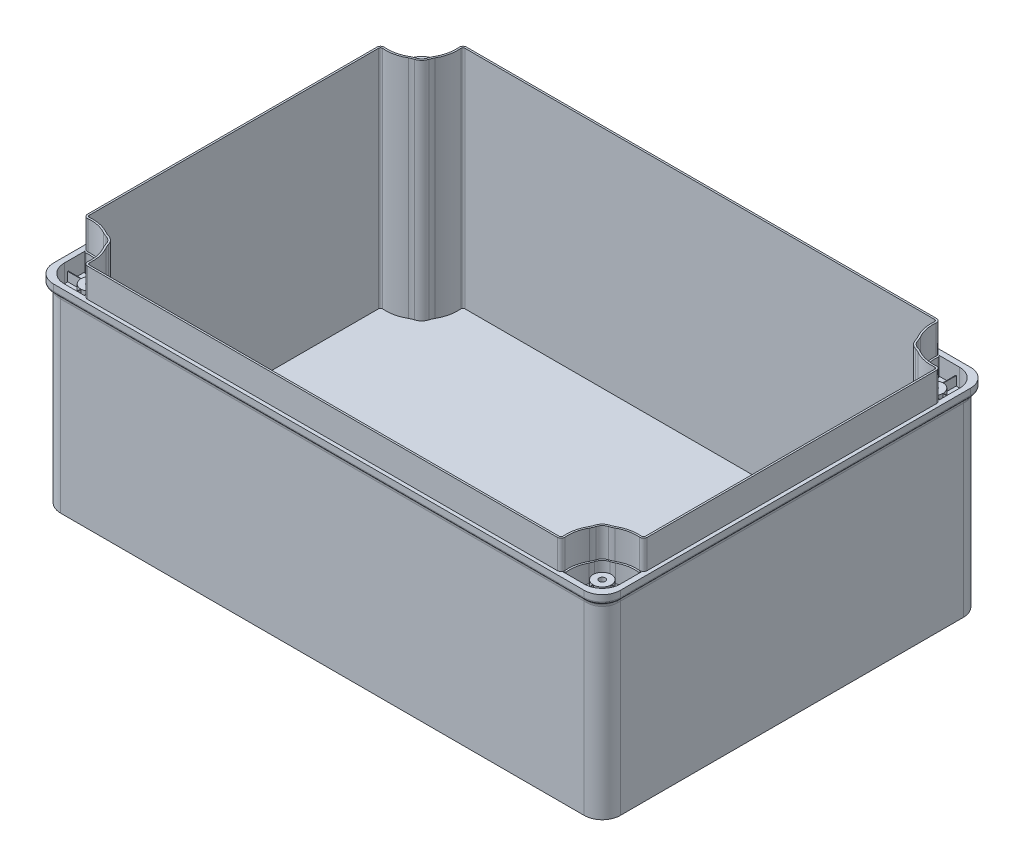
SolidWorks part; units mm, degrees
ref_plane "Alzado" through (0, 0, 0) normal (0, 0, 1) x (1, 0, 0)
ref_plane "Planta" through (0, 0, 0) normal (0, 1, 0) x (1, 0, 0)
ref_plane "Vista lateral" through (0, 0, 0) normal (1, 0, 0) x (0, 0, -1)
sketch "Croquis1" plane through (0, 0, 0) normal (0, 1, 0) x (1, 0, 0)
  line L0 (-154, 94) -> (-154, -94)
  line L1 (-145, 105) -> (145, 105)
  line L2 (-155, 95) -> (-155, -95)
  line L3 (-145, -105) -> (145, -105)
  line L4 (155, 95) -> (155, -95)
  line L5 (-155, 105) -> (155, -105) construction
  line L6 (-155, -105) -> (155, 105) construction
  line L7 (-144, -104) -> (144, -104)
  line L8 (154, 94) -> (154, -94)
  line L9 (-144, 104) -> (144, 104)
  line L10 (-155, 105) -> (-155, -105) construction
  line L11 (-155, -105) -> (155, -105) construction
  line L12 (-154, 104) -> (-154, -104) construction
  line L13 (-154, -104) -> (154, -104) construction
  line L14 (154, 104) -> (154, -104) construction
  line L15 (155, 105) -> (155, -105) construction
  line L16 (-154, 104) -> (154, 104) construction
  line L17 (-155, 105) -> (155, 105) construction
  arc A0 (-155, -95) -> (-145, -105) centre (-145, -95) ccw
  arc A1 (-154, -94) -> (-144, -104) centre (-144, -94) ccw
  arc A2 (144, -104) -> (154, -94) centre (144, -94) ccw
  arc A3 (145, -105) -> (155, -95) centre (145, -95) ccw
  arc A4 (154, 94) -> (144, 104) centre (144, 94) ccw
  arc A5 (145, 105) -> (155, 95) centre (145, 95) cw
  arc A6 (-145, 105) -> (-155, 95) centre (-145, 95) ccw
  arc A7 (-154, 94) -> (-144, 104) centre (-144, 94) cw
  point P0 (0, 0)
  dimension "D4" = 10
  dimension "D1" = 210
  dimension "D2" = 310
  dimension "D3" = 1
extrude "Saliente-Extruir1" add sketch "Croquis1" along normal blind 109
sketch "Croquis2" plane through (0, 0, 0) normal (0, -1, 0) x (1, 0, 0)
  line L1 (-145, 105) -> (145, 105)
  line L2 (-155, 95) -> (-155, -95)
  line L3 (-145, -105) -> (145, -105)
  line L4 (155, 95) -> (155, -95)
  line L5 (-155, 105) -> (155, -105) construction
  line L6 (-155, -105) -> (155, 105) construction
  arc A0 (145, -105) -> (155, -95) centre (145, -95) ccw
  arc A1 (-155, -95) -> (-145, -105) centre (-145, -95) ccw
  arc A2 (145, 105) -> (155, 95) centre (145, 95) cw
  arc A3 (-145, 105) -> (-155, 95) centre (-145, 95) ccw
  point P0 (0, 0)
  dimension "D3" = 10
  dimension "D1" = 210
  dimension "D2" = 310
extrude "Saliente-Extruir2" add sketch "Croquis2" along normal blind 1
sketch "Croquis19" plane through (0, 109, 0) normal (0, 1, 0) x (1, 0, 0)
sketch "Croquis32" plane through (0, 109, 0) normal (0, 1, 0) x (1, 0, 0)
  line L0 (-157, 97) -> (-157, -97)
  line L1 (-145, 105) -> (145, 105)
  line L2 (-155, 95) -> (-155, -95)
  line L3 (-145, -105) -> (145, -105)
  line L4 (155, 95) -> (155, -95)
  line L5 (-155, 105) -> (155, -105) construction
  line L6 (-155, -105) -> (155, 105) construction
  line L7 (-147, -107) -> (147, -107)
  line L8 (157, 97) -> (157, -97)
  line L9 (-147, 107) -> (147, 107)
  line L10 (-157, 107) -> (157, 107) construction
  line L11 (-157, 107) -> (-157, -107) construction
  line L12 (-155, 105) -> (-155, -105) construction
  line L13 (-155, 105) -> (155, 105) construction
  line L14 (-155, -105) -> (155, -105) construction
  line L15 (-157, -107) -> (157, -107) construction
  line L16 (155, 105) -> (155, -105) construction
  line L17 (157, 107) -> (157, -107) construction
  arc A0 (-147, 107) -> (-157, 97) centre (-147, 97) ccw
  arc A1 (-155, 95) -> (-145, 105) centre (-145, 95) cw
  arc A2 (-155, -95) -> (-145, -105) centre (-145, -95) ccw
  arc A3 (-157, -97) -> (-147, -107) centre (-147, -97) ccw
  arc A4 (145, -105) -> (155, -95) centre (145, -95) ccw
  arc A5 (147, -107) -> (157, -97) centre (147, -97) ccw
  arc A6 (157, 97) -> (147, 107) centre (147, 97) ccw
  arc A7 (155, 95) -> (145, 105) centre (145, 95) ccw
  point P0 (0, 0)
  dimension "D4" = 10
  dimension "D5" = 10
  dimension "D1" = 210
  dimension "D2" = 310
  dimension "D3" = 2
extrude "Saliente-Extruir5" add sketch "Croquis32" against normal blind 5
fillet "Redondeo3" radius 1.5 8 edges at (154.0711, 104, 104.0711) (0, 104, 107) (-154.0711, 104, 104.0711) (-157, 104, 0) (-154.0711, 104, -104.0711) (0, 104, -107) (154.0711, 104, -104.0711) (157, 104, 0)
fillet "Redondeo4" radius 3 8 edges at (-152.0711, 104, 102.0711) (-152.0711, 104, -102.0711) (152.0711, 104, -102.0711) (152.0711, 104, 102.0711) (0, 104, -105) (155, 104, 0) (0, 104, 105) (-155, 104, 0)
sketch "Croquis35" plane through (0, 109, 0) normal (0, 1, 0) x (1, 0, 0)
  line L0 (-154, 80.1598) -> (-154, 81.2867)
  line L2 (0, 0) -> (0, 134.5749) construction
  line L3 (-154, 94) -> (-154, -94) construction
  line L4 (-154, 94) -> (-154, 81.2867)
  line L5 (-154, 81.2867) -> (-154.0397, 94.0085)
  line L6 (-144.0085, 104.0397) -> (-131.2867, 104)
  line L7 (144, 104) -> (-144, 104) construction
  line L14 (0, 0) -> (185.7371, 0) construction
  line L15 (-131.2867, 104) -> (-130.1598, 104)
  line L22 (-131.2867, -104) -> (-130.1598, -104)
  line L23 (-144.0085, -104.0397) -> (-131.2867, -104)
  line L24 (-154, -81.2867) -> (-154.0397, -94.0085)
  line L25 (154, -81.2867) -> (154.0397, -94.0085)
  line L27 (-154, -80.1598) -> (-154, -81.2867)
  line L28 (154, -80.1598) -> (154, -81.2867)
  line L29 (-151.0711, 101.0711) -> (-133.1633, 83.1633) construction
  line L33 (154, 81.2867) -> (154.0397, 94.0085)
  line L34 (144.0085, 104.0397) -> (131.2867, 104)
  line L35 (131.2867, 104) -> (130.1598, 104)
  line L36 (154, 80.1598) -> (154, 81.2867)
  line L37 (131.2867, -104) -> (130.1598, -104)
  line L38 (144.0085, -104.0397) -> (131.2867, -104)
  arc A0 (-152.9081, 81.1556) -> (-141.0958, 83.7363) centre (-151.0711, 101.0711) ccw
  arc A1 (-144, 104) -> (-154, 94) centre (-144, 94) ccw construction
  arc A5 (-147, 107) -> (-157, 97) centre (-147, 97) ccw construction
  arc A6 (-154.0397, 94.0085) -> (-144.0085, 104.0397) centre (-144.0397, 94.0397) cw
  arc A13 (-130.1598, 104) -> (-131.1556, 102.9081) centre (-130.1598, 103) ccw
  arc A14 (-152.9081, 81.1556) -> (-154, 80.1598) centre (-153, 80.1598) ccw
  arc A18 (-133.7363, -91.0958) -> (-134.6911, -88.8308) centre (-125.0689, -86.1082) cw
  arc A23 (-130.1598, -104) -> (-131.1556, -102.9081) centre (-130.1598, -103) cw
  arc A24 (-154.0397, -94.0085) -> (-144.0085, -104.0397) centre (-144.0397, -94.0397) ccw
  arc A28 (-138.8308, 84.6911) -> (-134.6911, 88.8308) centre (-140.4645, 90.4645) ccw
  arc A30 (-133.7363, 91.0958) -> (-131.1556, 102.9081) centre (-151.0711, 101.0711) ccw
  arc A31 (-141.0958, 83.7363) -> (-138.8308, 84.6911) centre (-136.1082, 75.0689) cw
  arc A32 (-133.7363, 91.0958) -> (-134.6911, 88.8308) centre (-125.0689, 86.1082) ccw
  arc A33 (154.0397, 94.0085) -> (144.0085, 104.0397) centre (144.0397, 94.0397) ccw
  arc A34 (130.1598, 104) -> (131.1556, 102.9081) centre (130.1598, 103) cw
  arc A35 (-138.8308, -84.6911) -> (-134.6911, -88.8308) centre (-140.4645, -90.4645) cw
  arc A36 (133.7363, 91.0958) -> (134.6911, 88.8308) centre (125.0689, 86.1082) cw
  arc A37 (138.8308, 84.6911) -> (134.6911, 88.8308) centre (140.4645, 90.4645) cw
  arc A38 (141.0958, 83.7363) -> (138.8308, 84.6911) centre (136.1082, 75.0689) ccw
  arc A39 (152.9081, 81.1556) -> (141.0958, 83.7363) centre (151.0711, 101.0711) cw
  arc A40 (152.9081, 81.1556) -> (154, 80.1598) centre (153, 80.1598) cw
  arc A41 (-141.0958, -83.7363) -> (-138.8308, -84.6911) centre (-136.1082, -75.0689) ccw
  arc A42 (133.7363, 91.0958) -> (131.1556, 102.9081) centre (151.0711, 101.0711) cw
  arc A43 (-152.9081, -81.1556) -> (-141.0958, -83.7363) centre (-151.0711, -101.0711) cw
  arc A44 (-152.9081, -81.1556) -> (-154, -80.1598) centre (-153, -80.1598) cw
  arc A45 (154.0397, -94.0085) -> (144.0085, -104.0397) centre (144.0397, -94.0397) cw
  arc A46 (152.9081, -81.1556) -> (154, -80.1598) centre (153, -80.1598) ccw
  arc A47 (152.9081, -81.1556) -> (141.0958, -83.7363) centre (151.0711, -101.0711) ccw
  arc A48 (141.0958, -83.7363) -> (138.8308, -84.6911) centre (136.1082, -75.0689) cw
  arc A49 (138.8308, -84.6911) -> (134.6911, -88.8308) centre (140.4645, -90.4645) ccw
  arc A50 (133.7363, -91.0958) -> (134.6911, -88.8308) centre (125.0689, -86.1082) ccw
  arc A51 (133.7363, -91.0958) -> (131.1556, -102.9081) centre (151.0711, -101.0711) ccw
  arc A52 (130.1598, -104) -> (131.1556, -102.9081) centre (130.1598, -103) ccw
  arc A54 (-133.7363, -91.0958) -> (-131.1556, -102.9081) centre (-151.0711, -101.0711) cw
  point P30 (-154.0711, 104.0711)
  point P79 (-134.4926, 89.8838)
  line M5 (144, -104) -> (-144, -104)
  arc M6 (-144, -104) -> (-154, -94) centre (-144, -94) cw
  line M7 (-154, -94) -> (-154, 94)
  arc M8 (-154, 94) -> (-144, 104) centre (-144, 94) cw
  line M9 (-144, 104) -> (144, 104)
  arc M10 (144, 104) -> (154, 94) centre (144, 94) cw
  line M11 (154, 94) -> (154, -94)
  arc M12 (154, -94) -> (144, -104) centre (144, -94) cw
  dimension "D1" = 10
  dimension "D2" = 1
  dimension "D3" = 1
  dimension "D6" = 10
extrude "Saliente-Extruir6" add sketch "Croquis35" against normal blind 110 contours A0 M7 M9 M8 | M7 M6 M5 | M11 M5 M12 | M11 M10 M9 region at (-143.4094, 109, -93.4094) region at (-143.4094, 109, 93.4094) region at (143.4094, 109, -93.4094) region at (143.4094, 109, 93.4094)
sketch "Croquis36" plane through (0, 109, 0) normal (0, 1, 0) x (1, 0, 0)
  line L0 (-144, 104) -> (-133.311, 104)
  line L1 (-154, 94) -> (-154, 83.311)
  line L2 (0, 0) -> (0, 148.5327) construction
  line L3 (-154, 82.1692) -> (-154, 83.311)
  line L10 (-133.311, 104) -> (-132.1692, 104)
  line L11 (0, 0) -> (185.6369, 0) construction
  line L24 (154, 82.1692) -> (154, 83.311)
  line L26 (154, 94) -> (154, 83.311)
  line L27 (144, 104) -> (133.311, 104)
  line L28 (133.311, 104) -> (132.1692, 104)
  line L29 (-154, -82.1692) -> (-154, -83.311)
  line L30 (-154, -94) -> (-154, -83.311)
  line L31 (-144, -104) -> (-133.311, -104)
  line L32 (-133.311, -104) -> (-132.1692, -104)
  line L33 (133.311, -104) -> (132.1692, -104)
  line L34 (144, -104) -> (133.311, -104)
  line L35 (154, -94) -> (154, -83.311)
  line L36 (154, -82.1692) -> (154, -83.311)
  arc A4 (-152.8985, 83.1641) -> (-142.5598, 85.2105) centre (-151.0711, 101.0711) ccw
  arc A8 (-144, 104) -> (-154, 94) centre (-144, 94) ccw
  arc A11 (-152.8985, 83.1641) -> (-154, 82.1692) centre (-153, 82.1692) ccw
  arc A12 (-132.1692, 104) -> (-133.1641, 102.8985) centre (-132.1692, 103) ccw
  arc A27 (-140.3609, 86.0738) -> (-136.0738, 90.3609) centre (-141.8787, 91.8787) ccw
  arc A30 (-135.2105, 92.5598) -> (-133.1641, 102.8985) centre (-151.0711, 101.0711) ccw
  arc A31 (-142.5598, 85.2105) -> (-140.3609, 86.0738) centre (-137.8313, 76.3991) cw
  arc A32 (-135.2105, 92.5598) -> (-136.0738, 90.3609) centre (-126.3991, 87.8313) ccw
  arc A33 (152.8985, 83.1641) -> (154, 82.1692) centre (153, 82.1692) cw
  arc A34 (144, 104) -> (154, 94) centre (144, 94) cw
  arc A35 (132.1692, 104) -> (133.1641, 102.8985) centre (132.1692, 103) cw
  arc A36 (152.8985, -83.1641) -> (142.5598, -85.2105) centre (151.0711, -101.0711) ccw
  arc A37 (135.2105, 92.5598) -> (136.0738, 90.3609) centre (126.3991, 87.8313) cw
  arc A38 (140.3609, 86.0738) -> (136.0738, 90.3609) centre (141.8787, 91.8787) cw
  arc A39 (142.5598, 85.2105) -> (140.3609, 86.0738) centre (137.8313, 76.3991) ccw
  arc A40 (152.8985, 83.1641) -> (142.5598, 85.2105) centre (151.0711, 101.0711) cw
  arc A41 (135.2105, 92.5598) -> (133.1641, 102.8985) centre (151.0711, 101.0711) cw
  arc A42 (-152.8985, -83.1641) -> (-154, -82.1692) centre (-153, -82.1692) cw
  arc A43 (-144, -104) -> (-154, -94) centre (-144, -94) cw
  arc A44 (-132.1692, -104) -> (-133.1641, -102.8985) centre (-132.1692, -103) cw
  arc A45 (-135.2105, -92.5598) -> (-133.1641, -102.8985) centre (-151.0711, -101.0711) cw
  arc A46 (-135.2105, -92.5598) -> (-136.0738, -90.3609) centre (-126.3991, -87.8313) cw
  arc A47 (-140.3609, -86.0738) -> (-136.0738, -90.3609) centre (-141.8787, -91.8787) cw
  arc A48 (-142.5598, -85.2105) -> (-140.3609, -86.0738) centre (-137.8313, -76.3991) ccw
  arc A49 (-152.8985, -83.1641) -> (-142.5598, -85.2105) centre (-151.0711, -101.0711) cw
  arc A50 (142.5598, -85.2105) -> (140.3609, -86.0738) centre (137.8313, -76.3991) cw
  arc A51 (140.3609, -86.0738) -> (136.0738, -90.3609) centre (141.8787, -91.8787) ccw
  arc A52 (135.2105, -92.5598) -> (136.0738, -90.3609) centre (126.3991, -87.8313) ccw
  arc A54 (132.1692, -104) -> (133.1641, -102.8985) centre (132.1692, -103) ccw
  arc A55 (144, -104) -> (154, -94) centre (144, -94) ccw
  arc A56 (152.8985, -83.1641) -> (154, -82.1692) centre (153, -82.1692) ccw
  arc A57 (135.2105, -92.5598) -> (133.1641, -102.8985) centre (151.0711, -101.0711) ccw
  point P64 (-135.899, 91.3856)
  dimension "D1" = 10
  dimension "D2" = 1
  dimension "D5" = 10
extrude "Cortar-Extruir1" cut sketch "Croquis36" against normal blind 10
sketch "Croquis44" plane through (0, 99, 0) normal (0, 1, 0) x (1, 0, 0)
  arc A4 (-152.8985, 83.1641) -> (-142.5598, 85.2105) centre (-151.0711, 101.0711) ccw construction
  circle A5 centre (-141.8787, 91.8787) radius 5
  circle A6 centre (141.8787, 91.8787) radius 5
  circle A7 centre (141.8787, -91.8787) radius 5
  circle A8 centre (-141.8787, -91.8787) radius 5
extrude "Saliente-Extruir14" add sketch "Croquis44" along normal blind 5
sketch "Croquis45" plane through (0, 104, 0) normal (0, 1, 0) x (1, 0, 0)
  line L0 (0, 0) -> (0, 122.6826) construction
  line L1 (0, 0) -> (201.0584, 0) construction
  circle A0 centre (-141.8787, 91.8787) radius 1.7
  circle A1 centre (141.8787, 91.8787) radius 1.7
  circle A2 centre (141.8787, -91.8787) radius 1.7
  circle A3 centre (-141.8787, -91.8787) radius 1.7
extrude "Cortar-Extruir3" cut sketch "Croquis45" against normal blind 20
sketch "Croquis47" [suppressed] plane through (0, 99, 0) normal (0, 1, 0) x (1, 0, 0)
  line L0 (-141.8787, 91.8787) -> (-141.8787, 104) construction
  line L1 (-132.1692, 104) -> (-144, 104) construction
  line L2 (-141.8787, 91.8787) -> (-154, 91.8787) construction
  line L3 (0, 124.6965) -> (0, 0) construction
  line L4 (0, 0) -> (232.9458, 0) construction
  line L5 (142.0787, 95.8787) -> (142.0787, 104)
  line L6 (-154, 91.6787) -> (-145.8787, 91.6787)
  line L7 (-141.6787, 95.8787) -> (-141.6787, 104)
  line L8 (-154, 92.0787) -> (-145.8787, 92.0787)
  line L9 (-142.0787, 95.8787) -> (-142.0787, 104)
  line L10 (-142.0787, 104) -> (-141.6787, 104)
  line L11 (-142.0787, 95.8787) -> (-141.6787, 95.8787)
  line L12 (-145.8787, 92.0787) -> (-145.8787, 91.6787)
  line L13 (-154, 92.0787) -> (-154, 91.6787)
  line L14 (142.0787, 104) -> (141.6787, 104)
  line L15 (141.6787, 95.8787) -> (141.6787, 104)
  line L16 (142.0787, 95.8787) -> (141.6787, 95.8787)
  line L17 (154, 92.0787) -> (145.8787, 92.0787)
  line L18 (145.8787, 92.0787) -> (145.8787, 91.6787)
  line L19 (154, 91.6787) -> (145.8787, 91.6787)
  line L20 (154, 92.0787) -> (154, 91.6787)
  line L21 (154, -92.0787) -> (154, -91.6787)
  line L22 (154, -91.6787) -> (145.8787, -91.6787)
  line L23 (145.8787, -92.0787) -> (145.8787, -91.6787)
  line L24 (154, -92.0787) -> (145.8787, -92.0787)
  line L25 (142.0787, -95.8787) -> (141.6787, -95.8787)
  line L26 (141.6787, -95.8787) -> (141.6787, -104)
  line L27 (142.0787, -104) -> (141.6787, -104)
  line L28 (142.0787, -95.8787) -> (142.0787, -104)
  line L29 (-154, -92.0787) -> (-145.8787, -92.0787)
  line L30 (-145.8787, -92.0787) -> (-145.8787, -91.6787)
  line L31 (-154, -91.6787) -> (-145.8787, -91.6787)
  line L32 (-154, -92.0787) -> (-154, -91.6787)
  line L33 (-142.0787, -95.8787) -> (-142.0787, -104)
  line L34 (-142.0787, -104) -> (-141.6787, -104)
  line L35 (-141.6787, -95.8787) -> (-141.6787, -104)
  line L36 (-142.0787, -95.8787) -> (-141.6787, -95.8787)
extrude "Saliente-Extruir17" [suppressed] add sketch "Croquis47" along normal blind 5
sketch "Croquis55" plane through (0, 0, 0) normal (0, 1, 0) x (1, 0, 0)
  line L8 (130.1598, 105) -> (-130.1598, 105)
  line L9 (-155, 80.1598) -> (-155, -80.1598)
  line L10 (-130.1598, -105) -> (130.1598, -105)
  line L11 (155, -80.1598) -> (155, 80.1598)
  line L12 (130.1598, 105) -> (-130.1598, 105)
  line L13 (-155, 80.1598) -> (-155, -80.1598)
  line L14 (-130.1598, -105) -> (130.1598, -105)
  line L15 (155, -80.1598) -> (155, 80.1598)
  arc A56 (132.1514, 102.8163) -> (134.603, 91.5946) centre (151.0711, 101.0711) ccw
  arc A57 (132.1514, 102.8163) -> (130.1598, 105) centre (130.1598, 103) ccw
  arc A58 (-130.1598, 105) -> (-132.1514, 102.8163) centre (-130.1598, 103) ccw
  arc A59 (-134.603, 91.5946) -> (-132.1514, 102.8163) centre (-151.0711, 101.0711) ccw
  arc A60 (-134.603, 91.5946) -> (-135.6534, 89.1031) centre (-125.0689, 86.1082) ccw
  arc A61 (-139.1031, 85.6534) -> (-135.6534, 89.1031) centre (-140.4645, 90.4645) ccw
  arc A62 (-139.1031, 85.6534) -> (-141.5946, 84.603) centre (-136.1082, 75.0689) ccw
  arc A63 (-152.8163, 82.1514) -> (-141.5946, 84.603) centre (-151.0711, 101.0711) ccw
  arc A64 (-152.8163, 82.1514) -> (-155, 80.1598) centre (-153, 80.1598) ccw
  arc A65 (-155, -80.1598) -> (-152.8163, -82.1514) centre (-153, -80.1598) ccw
  arc A66 (-141.5946, -84.603) -> (-152.8163, -82.1514) centre (-151.0711, -101.0711) ccw
  arc A67 (-141.5946, -84.603) -> (-139.1031, -85.6534) centre (-136.1082, -75.0689) ccw
  arc A68 (-135.6534, -89.1031) -> (-139.1031, -85.6534) centre (-140.4645, -90.4645) ccw
  arc A69 (-135.6534, -89.1031) -> (-134.603, -91.5946) centre (-125.0689, -86.1082) ccw
  arc A70 (-132.1514, -102.8163) -> (-134.603, -91.5946) centre (-151.0711, -101.0711) ccw
  arc A71 (-132.1514, -102.8163) -> (-130.1598, -105) centre (-130.1598, -103) ccw
  arc A72 (130.1598, -105) -> (132.1514, -102.8163) centre (130.1598, -103) ccw
  arc A73 (134.603, -91.5946) -> (132.1514, -102.8163) centre (151.0711, -101.0711) ccw
  arc A74 (134.603, -91.5946) -> (135.6534, -89.1031) centre (125.0689, -86.1082) ccw
  arc A75 (139.1031, -85.6534) -> (135.6534, -89.1031) centre (140.4645, -90.4645) ccw
  arc A76 (139.1031, -85.6534) -> (141.5946, -84.603) centre (136.1082, -75.0689) ccw
  arc A77 (152.8163, -82.1514) -> (141.5946, -84.603) centre (151.0711, -101.0711) ccw
  arc A78 (152.8163, -82.1514) -> (155, -80.1598) centre (153, -80.1598) ccw
  arc A79 (155, 80.1598) -> (152.8163, 82.1514) centre (153, 80.1598) ccw
  arc A80 (141.5946, 84.603) -> (152.8163, 82.1514) centre (151.0711, 101.0711) ccw
  arc A81 (141.5946, 84.603) -> (139.1031, 85.6534) centre (136.1082, 75.0689) ccw
  arc A82 (135.6534, 89.1031) -> (139.1031, 85.6534) centre (140.4645, 90.4645) ccw
  arc A83 (135.6534, 89.1031) -> (134.603, 91.5946) centre (125.0689, 86.1082) ccw
  arc A84 (132.1514, 102.8163) -> (134.603, 91.5946) centre (151.0711, 101.0711) ccw
  arc A85 (132.1514, 102.8163) -> (130.1598, 105) centre (130.1598, 103) ccw
  arc A86 (-130.1598, 105) -> (-132.1514, 102.8163) centre (-130.1598, 103) ccw
  arc A87 (-134.603, 91.5946) -> (-132.1514, 102.8163) centre (-151.0711, 101.0711) ccw
  arc A88 (-134.603, 91.5946) -> (-135.6534, 89.1031) centre (-125.0689, 86.1082) ccw
  arc A89 (-139.1031, 85.6534) -> (-135.6534, 89.1031) centre (-140.4645, 90.4645) ccw
  arc A90 (-139.1031, 85.6534) -> (-141.5946, 84.603) centre (-136.1082, 75.0689) ccw
  arc A91 (-152.8163, 82.1514) -> (-141.5946, 84.603) centre (-151.0711, 101.0711) ccw
  arc A92 (-152.8163, 82.1514) -> (-155, 80.1598) centre (-153, 80.1598) ccw
  arc A93 (-155, -80.1598) -> (-152.8163, -82.1514) centre (-153, -80.1598) ccw
  arc A94 (-141.5946, -84.603) -> (-152.8163, -82.1514) centre (-151.0711, -101.0711) ccw
  arc A95 (-141.5946, -84.603) -> (-139.1031, -85.6534) centre (-136.1082, -75.0689) ccw
  arc A96 (-135.6534, -89.1031) -> (-139.1031, -85.6534) centre (-140.4645, -90.4645) ccw
  arc A97 (-135.6534, -89.1031) -> (-134.603, -91.5946) centre (-125.0689, -86.1082) ccw
  arc A98 (-132.1514, -102.8163) -> (-134.603, -91.5946) centre (-151.0711, -101.0711) ccw
  arc A99 (-132.1514, -102.8163) -> (-130.1598, -105) centre (-130.1598, -103) ccw
  arc A100 (130.1598, -105) -> (132.1514, -102.8163) centre (130.1598, -103) ccw
  arc A101 (134.603, -91.5946) -> (132.1514, -102.8163) centre (151.0711, -101.0711) ccw
  arc A102 (134.603, -91.5946) -> (135.6534, -89.1031) centre (125.0689, -86.1082) ccw
  arc A103 (139.1031, -85.6534) -> (135.6534, -89.1031) centre (140.4645, -90.4645) ccw
  arc A104 (139.1031, -85.6534) -> (141.5946, -84.603) centre (136.1082, -75.0689) ccw
  arc A105 (152.8163, -82.1514) -> (141.5946, -84.603) centre (151.0711, -101.0711) ccw
  arc A106 (152.8163, -82.1514) -> (155, -80.1598) centre (153, -80.1598) ccw
  arc A107 (155, 80.1598) -> (152.8163, 82.1514) centre (153, 80.1598) ccw
  arc A108 (141.5946, 84.603) -> (152.8163, 82.1514) centre (151.0711, 101.0711) ccw
  arc A109 (141.5946, 84.603) -> (139.1031, 85.6534) centre (136.1082, 75.0689) ccw
  arc A110 (135.6534, 89.1031) -> (139.1031, 85.6534) centre (140.4645, 90.4645) ccw
  arc A111 (135.6534, 89.1031) -> (134.603, 91.5946) centre (125.0689, 86.1082) ccw
  dimension "D1" = 1
extrude "Saliente-Extruir19" add sketch "Croquis55" along normal blind 125 contours A84 A111 A110 A109 A108 A107 L15 A106 A105 A104 A103 A102 A101 A100 L14 A99 A98 A97 A96 A95 A94 A93 L13 A92 A91 A90 A89 A88 A87 A86 L12 A85
sketch "Croquis56" plane through (0, 125, 0) normal (0, 1, 0) x (1, 0, 0)
  line L8 (130.1598, 104) -> (-130.1598, 104)
  line L9 (-154, 80.1598) -> (-154, -80.1598)
  line L10 (-130.1598, -104) -> (130.1598, -104)
  line L11 (154, -80.1598) -> (154, 80.1598)
  line L12 (130.1598, 104) -> (-130.1598, 104)
  line L13 (-154, 80.1598) -> (-154, -80.1598)
  line L14 (-130.1598, -104) -> (130.1598, -104)
  line L15 (154, -80.1598) -> (154, 80.1598)
  arc A56 (131.1556, 102.9081) -> (130.1598, 104) centre (130.1598, 103) ccw
  arc A57 (-130.1598, 104) -> (-131.1556, 102.9081) centre (-130.1598, 103) ccw
  arc A58 (-133.7363, 91.0958) -> (-131.1556, 102.9081) centre (-151.0711, 101.0711) ccw
  arc A59 (-133.7363, 91.0958) -> (-134.6911, 88.8308) centre (-125.0689, 86.1082) ccw
  arc A60 (-138.8308, 84.6911) -> (-134.6911, 88.8308) centre (-140.4645, 90.4645) ccw
  arc A61 (-138.8308, 84.6911) -> (-141.0958, 83.7363) centre (-136.1082, 75.0689) ccw
  arc A62 (-152.9081, 81.1556) -> (-141.0958, 83.7363) centre (-151.0711, 101.0711) ccw
  arc A63 (-152.9081, 81.1556) -> (-154, 80.1598) centre (-153, 80.1598) ccw
  arc A64 (-154, -80.1598) -> (-152.9081, -81.1556) centre (-153, -80.1598) ccw
  arc A65 (-141.0958, -83.7363) -> (-152.9081, -81.1556) centre (-151.0711, -101.0711) ccw
  arc A66 (-141.0958, -83.7363) -> (-138.8308, -84.6911) centre (-136.1082, -75.0689) ccw
  arc A67 (-134.6911, -88.8308) -> (-138.8308, -84.6911) centre (-140.4645, -90.4645) ccw
  arc A68 (-134.6911, -88.8308) -> (-133.7363, -91.0958) centre (-125.0689, -86.1082) ccw
  arc A69 (-131.1556, -102.9081) -> (-133.7363, -91.0958) centre (-151.0711, -101.0711) ccw
  arc A70 (-131.1556, -102.9081) -> (-130.1598, -104) centre (-130.1598, -103) ccw
  arc A71 (130.1598, -104) -> (131.1556, -102.9081) centre (130.1598, -103) ccw
  arc A72 (133.7363, -91.0958) -> (131.1556, -102.9081) centre (151.0711, -101.0711) ccw
  arc A73 (133.7363, -91.0958) -> (134.6911, -88.8308) centre (125.0689, -86.1082) ccw
  arc A74 (138.8308, -84.6911) -> (134.6911, -88.8308) centre (140.4645, -90.4645) ccw
  arc A75 (138.8308, -84.6911) -> (141.0958, -83.7363) centre (136.1082, -75.0689) ccw
  arc A76 (152.9081, -81.1556) -> (141.0958, -83.7363) centre (151.0711, -101.0711) ccw
  arc A77 (152.9081, -81.1556) -> (154, -80.1598) centre (153, -80.1598) ccw
  arc A78 (154, 80.1598) -> (152.9081, 81.1556) centre (153, 80.1598) ccw
  arc A79 (141.0958, 83.7363) -> (152.9081, 81.1556) centre (151.0711, 101.0711) ccw
  arc A80 (141.0958, 83.7363) -> (138.8308, 84.6911) centre (136.1082, 75.0689) ccw
  arc A81 (134.6911, 88.8308) -> (138.8308, 84.6911) centre (140.4645, 90.4645) ccw
  arc A82 (134.6911, 88.8308) -> (133.7363, 91.0958) centre (125.0689, 86.1082) ccw
  arc A83 (131.1556, 102.9081) -> (133.7363, 91.0958) centre (151.0711, 101.0711) ccw
  arc A84 (131.1556, 102.9081) -> (130.1598, 104) centre (130.1598, 103) ccw
  arc A85 (-130.1598, 104) -> (-131.1556, 102.9081) centre (-130.1598, 103) ccw
  arc A86 (-133.7363, 91.0958) -> (-131.1556, 102.9081) centre (-151.0711, 101.0711) ccw
  arc A87 (-133.7363, 91.0958) -> (-134.6911, 88.8308) centre (-125.0689, 86.1082) ccw
  arc A88 (-138.8308, 84.6911) -> (-134.6911, 88.8308) centre (-140.4645, 90.4645) ccw
  arc A89 (-138.8308, 84.6911) -> (-141.0958, 83.7363) centre (-136.1082, 75.0689) ccw
  arc A90 (-152.9081, 81.1556) -> (-141.0958, 83.7363) centre (-151.0711, 101.0711) ccw
  arc A91 (-152.9081, 81.1556) -> (-154, 80.1598) centre (-153, 80.1598) ccw
  arc A92 (-154, -80.1598) -> (-152.9081, -81.1556) centre (-153, -80.1598) ccw
  arc A93 (-141.0958, -83.7363) -> (-152.9081, -81.1556) centre (-151.0711, -101.0711) ccw
  arc A94 (-141.0958, -83.7363) -> (-138.8308, -84.6911) centre (-136.1082, -75.0689) ccw
  arc A95 (-134.6911, -88.8308) -> (-138.8308, -84.6911) centre (-140.4645, -90.4645) ccw
  arc A96 (-134.6911, -88.8308) -> (-133.7363, -91.0958) centre (-125.0689, -86.1082) ccw
  arc A97 (-131.1556, -102.9081) -> (-133.7363, -91.0958) centre (-151.0711, -101.0711) ccw
  arc A98 (-131.1556, -102.9081) -> (-130.1598, -104) centre (-130.1598, -103) ccw
  arc A99 (130.1598, -104) -> (131.1556, -102.9081) centre (130.1598, -103) ccw
  arc A100 (133.7363, -91.0958) -> (131.1556, -102.9081) centre (151.0711, -101.0711) ccw
  arc A101 (133.7363, -91.0958) -> (134.6911, -88.8308) centre (125.0689, -86.1082) ccw
  arc A102 (138.8308, -84.6911) -> (134.6911, -88.8308) centre (140.4645, -90.4645) ccw
  arc A103 (138.8308, -84.6911) -> (141.0958, -83.7363) centre (136.1082, -75.0689) ccw
  arc A104 (152.9081, -81.1556) -> (141.0958, -83.7363) centre (151.0711, -101.0711) ccw
  arc A105 (152.9081, -81.1556) -> (154, -80.1598) centre (153, -80.1598) ccw
  arc A106 (154, 80.1598) -> (152.9081, 81.1556) centre (153, 80.1598) ccw
  arc A107 (141.0958, 83.7363) -> (152.9081, 81.1556) centre (151.0711, 101.0711) ccw
  arc A108 (141.0958, 83.7363) -> (138.8308, 84.6911) centre (136.1082, 75.0689) ccw
  arc A109 (134.6911, 88.8308) -> (138.8308, 84.6911) centre (140.4645, 90.4645) ccw
  arc A110 (134.6911, 88.8308) -> (133.7363, 91.0958) centre (125.0689, 86.1082) ccw
  arc A111 (131.1556, 102.9081) -> (133.7363, 91.0958) centre (151.0711, 101.0711) ccw
  dimension "D1" = 1
extrude "Cortar-Extruir5" cut sketch "Croquis56" against normal blind 125 contours A84 L12 A85 A86 A87 A88 A89 A90 A91 L13 A92 A93 A94 A95 A96 A97 A98 L14 A99 A100 A101 A102 A103 A104 A105 L15 A106 A107 A108 A109 A110 A111
sketch "Croquis57" plane through (0, 99, 0) normal (0, 1, 0) x (1, 0, 0)
  line L0 (0, 0) -> (0, 127.8017) construction
  line L1 (143.5766, 91.9637) -> (143.5766, 91.7937)
  line L2 (0, 0) -> (185.7953, 0) construction
  line L3 (-143.5766, 91.9637) -> (-143.5766, 91.7937)
  line L4 (-141.7937, 93.5766) -> (-141.6787, 104)
  line L5 (-141.9637, 93.5766) -> (-142.0787, 104)
  line L6 (-143.5766, 91.9637) -> (-154, 92.0787)
  line L7 (-143.5766, 91.7937) -> (-154, 91.6787)
  line L10 (-154, 92.0787) -> (-154, 91.6787)
  line L11 (-142.0787, 104) -> (-141.6787, 104)
  line L12 (143.5766, 91.7937) -> (154, 91.6787)
  line L13 (-141.9637, 93.5766) -> (-141.7937, 93.5766)
  line L14 (154, 92.0787) -> (154, 91.6787)
  line L15 (143.5766, 91.9637) -> (154, 92.0787)
  line L16 (141.9637, 93.5766) -> (141.7937, 93.5766)
  line L17 (141.7937, 93.5766) -> (141.6787, 104)
  line L18 (142.0787, 104) -> (141.6787, 104)
  line L19 (141.9637, 93.5766) -> (142.0787, 104)
  line L20 (143.5766, -91.9637) -> (154, -92.0787)
  line L21 (154, -92.0787) -> (154, -91.6787)
  line L22 (143.5766, -91.7937) -> (154, -91.6787)
  line L23 (143.5766, -91.9637) -> (143.5766, -91.7937)
  line L24 (141.9637, -93.5766) -> (142.0787, -104)
  line L25 (142.0787, -104) -> (141.6787, -104)
  line L26 (141.7937, -93.5766) -> (141.6787, -104)
  line L27 (141.9637, -93.5766) -> (141.7937, -93.5766)
  line L28 (-141.9637, -93.5766) -> (-141.7937, -93.5766)
  line L29 (-141.7937, -93.5766) -> (-141.6787, -104)
  line L30 (-142.0787, -104) -> (-141.6787, -104)
  line L31 (-141.9637, -93.5766) -> (-142.0787, -104)
  line L32 (-143.5766, -91.9637) -> (-143.5766, -91.7937)
  line L33 (-143.5766, -91.7937) -> (-154, -91.6787)
  line L34 (-154, -92.0787) -> (-154, -91.6787)
  line L35 (-143.5766, -91.9637) -> (-154, -92.0787)
  circle A0 centre (-141.8787, 91.8787) radius 1.7 construction
extrude "Saliente-Extruir20" add sketch "Croquis57" along normal blind 5
sketch "Croquis58" plane through (0, 109, 0) normal (0, 1, 0) x (1, 0, 0)
  point P2 (0, 0)
sketch "Croquis59" plane through (0, 109, 0) normal (0, 1, 0) x (1, 0, 0)
sketch "Croquis60" plane through (0, 84, 0) normal (0, 1, 0) x (1, 0, 0)
sketch "Croquis43" plane through (0, 0, 0) normal (0, 1, 0) x (1, 0, 0)
